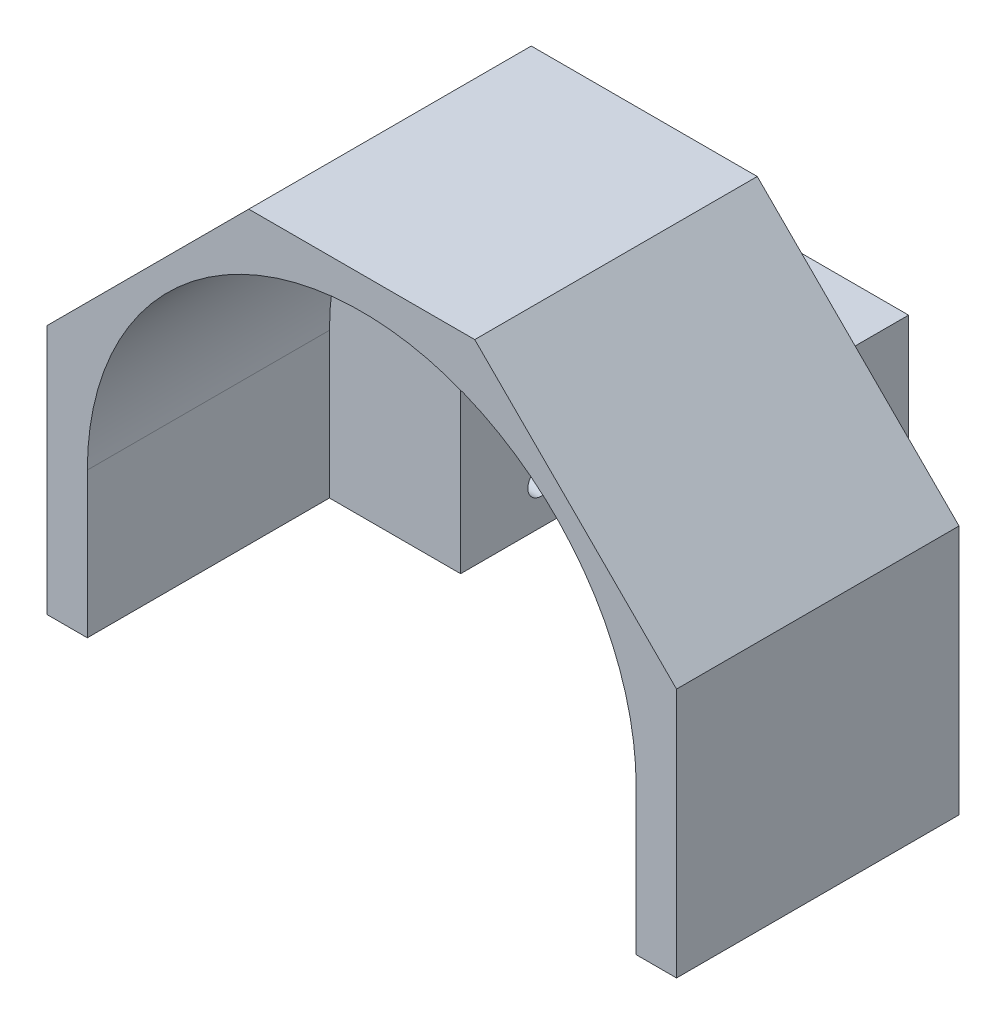
SolidWorks part; units mm, degrees
ref_plane "Plan de face" through (0, 0, 0) normal (0, 0, 1) x (1, 0, 0)
ref_plane "Plan de dessus" through (0, 0, 0) normal (0, 1, 0) x (1, 0, 0)
ref_plane "Plan de droite" through (0, 0, 0) normal (1, 0, 0) x (0, 0, -1)
ref_plane "Plan2" through (0, -10, 0) normal (0, 1, 0) x (1, 0, 0)
sketch "Esquisse3" plane through (0, 0, 0) normal (0, 0, 1) x (1, 0, 0)
  line L1 (-39, 28) -> (39, 28)
  line L2 (-39, 28) -> (-39, -28)
  line L3 (-39, -28) -> (39, -28)
  line L4 (39, 28) -> (39, -28)
  point P4 (0, 28)
  point P5 (-39, 0)
  point P8 (39, 0)
  point P9 (0, -28)
  dimension "D1" = 78
  dimension "D2" = 56
extrude "Boss.-Extru.2" add sketch "Esquisse3" along normal blind 45
sketch "Esquisse4" plane through (0, 0, 45) normal (0, 0, 1) x (1, 0, 0)
  line L2 (39, 28) -> (-39, 28) construction
  line L3 (24.75, -10) -> (-24.75, -10) construction
  circle A0 centre (0, -10) radius 34
  point P2 (0, 28)
  dimension "D1" = 68
extrude "Enlèv. mat.-Extru.1" cut sketch "Esquisse4" against normal blind 30
sketch "Esquisse5" plane through (0, 0, 0) normal (0, 0, -1) x (-1, 0, 0)
  line L0 (39, -28) -> (-39, -28) construction
  line L1 (-17.75, 7.5) -> (17.75, 7.5)
  line L2 (-17.75, 7.5) -> (-17.75, -28)
  line L3 (-17.75, -28) -> (17.75, -28)
  line L4 (17.75, 7.5) -> (17.75, -28)
  point P6 (0, -28)
  dimension "D1" = 35.5
  dimension "D2" = 35.5
extrude "Enlèv. mat.-Extru.2" cut sketch "Esquisse5" against normal up to surface (15 mm away) up to face at (0, -2, 15)
sketch "Esquisse8" plane through (0, 0, 0) normal (0, 0, -1) x (-1, 0, 0)
  line L0 (-22.75, -28) -> (-22.75, 12.5)
  line L1 (-17.75, -28) -> (-39, -28) construction
  line L2 (-22.75, 12.5) -> (22.75, 12.5)
  line L3 (22.75, 12.5) -> (22.75, -28)
  line L4 (39, -28) -> (17.75, -28) construction
  line L5 (22.75, -28) -> (39, -28)
  line L6 (39, -28) -> (39, 28)
  line L7 (39, 28) -> (-39, 28)
  line L8 (-39, 28) -> (-39, -28)
  line L9 (-39, -28) -> (-22.75, -28)
  line L10 (17.75, 7.5) -> (-17.75, 7.5) construction
  line L11 (-17.75, 7.5) -> (-17.75, -28) construction
  line L12 (17.75, -28) -> (17.75, 7.5) construction
  dimension "D1" = 5
  dimension "D2" = 5
  dimension "D3" = 5
extrude "Enlèv. mat.-Extru.5" cut sketch "Esquisse8" against normal blind 10
sketch "Esquisse12" plane through (0, 0, 45) normal (0, 0, 1) x (1, 0, 0)
  line L0 (-39, -28) -> (-28.8444, -28) construction
  line L1 (-34, -28) -> (34, -28)
  line L2 (-34, -28) -> (-34, -10)
  line L3 (-34, -10) -> (34, -10)
  line L4 (34, -28) -> (34, -10)
  line L5 (24.75, -10) -> (-24.75, -10) construction
  arc A0 (28.8444, -28) -> (-28.8444, -28) centre (0, -10) ccw construction
extrude "Enlèv. mat.-Extru.6" cut sketch "Esquisse12" against normal up to surface (30 mm away) up to face at (0, -7.5, 15)
sketch "Esquisse13" plane through (-22.75, 0, 0) normal (-1, 0, 0) x (0, 0, 1)
  line L0 (0, 12.5) -> (0, -28) construction
  line L1 (10, -28) -> (0, -28) construction
  circle A0 centre (5, -23) radius 1.6715
  dimension "D1" = 5
  dimension "D2" = 5
extrude "Enlèv. mat.-Extru.7" cut sketch "Esquisse13" against normal through all
sketch "Esquisse15" plane through (-22.75, 0, 0) normal (-1, 0, 0) x (0, 0, 1)
  line L0 (10, 12.5) -> (0, 12.5) construction
  line L1 (0, 12.5) -> (0, -28) construction
  circle A0 centre (5, 2.5) radius 1.5
  dimension "D1" = 3
  dimension "D2" = 10
  dimension "D3" = 5
extrude "Enlèv. mat.-Extru.8" cut sketch "Esquisse15" against normal through all
sketch "Esquisse16" plane through (0, 0, 15) normal (0, 0, 1) x (1, 0, 0)
  line L0 (-17.75, -28) -> (-17.75, 7.5) construction
  line L1 (-21.75, 3.5) -> (-13.75, 3.5)
  line L2 (-21.75, 3.5) -> (-21.75, 11.5)
  line L3 (-21.75, 11.5) -> (-13.75, 11.5)
  line L4 (-13.75, 3.5) -> (-13.75, 11.5)
  line L6 (-17.75, 7.5) -> (17.75, 7.5) construction
  dimension "D1" = 4
  dimension "D2" = 4
  dimension "D3" = 4
  dimension "D4" = 4
extrude "Enlèv. mat.-Extru.9" cut sketch "Esquisse16" against normal blind 4
sketch "Esquisse17" plane through (0, 12.5, 0) normal (0, 1, 0) x (1, 0, 0)
  line L0 (-22.75, -10) -> (-22.75, 0) construction
  line L1 (22.75, 0) -> (-22.75, 0) construction
  circle A0 centre (-12.75, -5) radius 1.5
  dimension "D1" = 3
  dimension "D2" = 10
  dimension "D3" = 5
extrude "Enlèv. mat.-Extru.10" cut sketch "Esquisse17" against normal through all
sketch "Esquisse18" plane through (0, 12.5, 0) normal (0, 1, 0) x (1, 0, 0)
  line L0 (22.75, -10) -> (22.75, 0) construction
  circle A0 centre (12.75, -5) radius 1.5
  dimension "D1" = 3
  dimension "D2" = 5
  dimension "D3" = 10
extrude "Enlèv. mat.-Extru.11" cut sketch "Esquisse18" against normal through all
sketch "Esquisse19" plane through (0, 0, 15) normal (0, 0, 1) x (1, 0, 0)
  line L0 (17.75, 7.5) -> (17.75, -28) construction
  line L1 (13.75, 11.5) -> (21.75, 11.5)
  line L2 (13.75, 11.5) -> (13.75, 3.5)
  line L3 (13.75, 3.5) -> (21.75, 3.5)
  line L4 (21.75, 11.5) -> (21.75, 3.5)
  line L5 (-13.75, 7.5) -> (17.75, 7.5) construction
  dimension "D1" = 4
  dimension "D2" = 4
  dimension "D3" = 4
  dimension "D4" = 4
extrude "Enlèv. mat.-Extru.12" cut sketch "Esquisse19" against normal blind 4
sketch "Esquisse20" plane through (0, 0, 45) normal (0, 0, 1) x (1, 0, 0)
  line L0 (-39, 3) -> (-39, 28)
  line L2 (-39, 28) -> (-14, 28)
  line L3 (39, 28) -> (-39, 28) construction
  line L4 (-14, 28) -> (-39, 3)
  line L5 (-39, 28) -> (-39, -28) construction
  point P2 (-39, 4.4644)
  point P8 (-14.3534, 28)
  dimension "D1" = 25
extrude "Enlèv. mat.-Extru.13" cut sketch "Esquisse20" against normal through all
mirror "Symétrie1" about plane through (0, 0, 0) normal (1, 0, 0) of "Enlèv. mat.-Extru.13"
